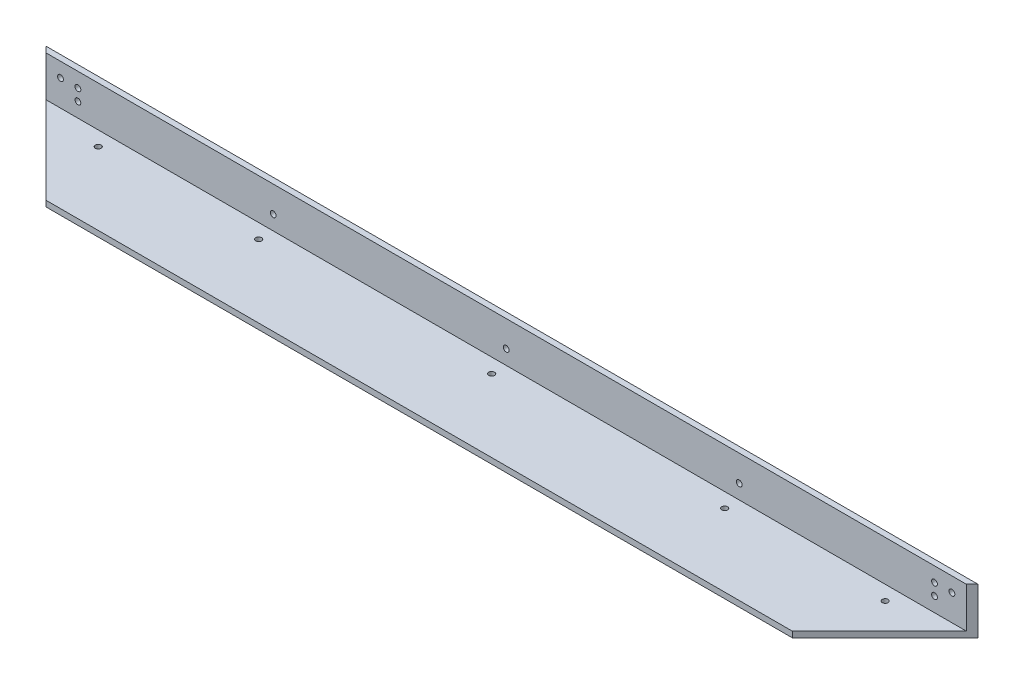
SolidWorks part; units mm, degrees
ref_plane "Front Plane" through (0, 0, 0) normal (0, 0, 1) x (1, 0, 0)
ref_plane "Top Plane" through (0, 0, 0) normal (0, 1, 0) x (1, 0, 0)
ref_plane "Right Plane" through (0, 0, 0) normal (1, 0, 0) x (0, 0, -1)
sketch "Sketch1" plane through (0, 0, 0) normal (1, 0, 0) x (0, 0, -1)
  line L0 (0, 0) -> (-50.8, 0)
  line L1 (-50.8, 0) -> (-50.8, 3.175)
  line L2 (-50.8, 3.175) -> (-3.175, 3.175)
  line L3 (-3.175, 3.175) -> (-3.175, 25.4)
  line L4 (-3.175, 25.4) -> (0, 25.4)
  line L5 (0, 25.4) -> (0, 0)
  dimension "LHeight" = 25.4
  dimension "LWidth" = 50.8
  dimension "LMaterialThickness" = 3.175
  dimension "D1" = 47.625
  dimension "D2" = 22.225
  dimension "D3" = 3.175
extrude "Boss-Extrude1" add sketch "Sketch1" along normal blind 510
chamfer "Chamfer6" distance 50.8 angle 45 1 edges at (510, 1.5875, 50.8)
chamfer "Chamfer7" distance 50.8 angle 45 1 edges at (0, 1.5875, 50.8)
sketch "BackSideHoles-Sketch2" plane through (0, 0, 0) normal (0, 0, -1) x (-1, 0, 0)
  line L0 (0, 0) -> (0, 25.4) construction
  line L1 (-510, 0) -> (0, 0) construction
  line L2 (-510, 0) -> (-510, 25.4) construction
  line L3 (-510, 25.4) -> (0, 25.4) construction
  circle A0 centre (-498.8875, 17.4625) radius 1.5875
  circle A1 centre (-489.3625, 17.4625) radius 1.5875
  circle A2 centre (-20.6375, 17.4625) radius 1.5875
  circle A4 centre (-11.1125, 17.4625) radius 1.5875
  circle A5 centre (-20.6375, 11.1125) radius 1.5875
  circle A6 centre (-489.3625, 11.1125) radius 1.5875
  circle A8 centre (-382.5, 11.1125) radius 1.5875
  circle A9 centre (-255, 11.1125) radius 1.5875
  circle A10 centre (-127.5, 11.1125) radius 1.5875
  dimension "D5" = 3.175
  dimension "D2" = 20.6375
  dimension "D4" = 20.6375
  dimension "D8" = 127.5
  dimension "D9" = 127.5
  dimension "D10" = 127.5
  dimension "D11" = 11.1125
  dimension "D6" = 7.9375
  dimension "D7" = 11.1125
  dimension "D3" = 11.1125
sketch "BottomHoles-Sketch3" plane through (0, 0, 0) normal (0, -1, 0) x (1, 0, 0)
  line L0 (510, 0) -> (0, 0) construction
  circle A7 centre (39.6875, 11.1125) radius 1.5875
  circle A8 centre (470.3125, 11.1125) radius 1.5875
  circle A9 centre (127.5, 11.1125) radius 1.5875
  circle A10 centre (255, 11.1125) radius 1.5875
  circle A11 centre (382.5, 11.1125) radius 1.5875
  dimension "D5" = 3.175
  dimension "D2" = 39.6875
  dimension "D3" = 39.6875
  dimension "D4" = 11.1125
  dimension "D1" = 127.5
  dimension "D6" = 127.5
  dimension "D7" = 127.5
extrude "BottomHoles-Cut-Extrude1" cut sketch "BottomHoles-Sketch3" against normal through all
extrude "BackSideHoles-Cut-Extrude2" cut sketch "BackSideHoles-Sketch2" against normal through all
equation "\"LowerRailWidth\"= 2.00in"
equation "\"LowerRailHeight\"= 1.00in"
equation "\"RailThickness\"= .125in'Spec"
equation "\"SideRailHoleX1FromSide\"= \"HoleOffsetFromSide\""
equation "\"SideRailHoleX2FromSide\"= \"VSWidth\" - \"HoleOffsetFromEdge\" - \"RailThickness\"'Equals 20.6375"
equation "\"SideRailHoleY1FromEdge\"= \"HoleOffsetFromEdge\""
equation "\"FrontBackRailLength\"= 510mm"
equation "\"VSWidth\"= 1.25in'Spec"
equation "\"HoleOffsetFromEdge\"= \"RailThickness\" * 2.5"
equation "\"HoleOffsetFromSide\"= \"RailThickness\" * 3.5"
equation "\"SideRailHoleY2FromSide\"= \"HoleOffsetFromSide\""
equation "\"FasteningHoleDiameter\"= .125in"
equation "\"D1@Boss-Extrude1\"=\"FrontBackRailLength\""
equation "\"D1@Chamfer6\"=\"LowerRailWidth\""
equation "\"D1@Chamfer7\"=\"LowerRailWidth\""
equation "\"D2@BackSideHoles-Sketch2\" = \"SideRailHoleX2FromSide\""
equation "\"D4@BackSideHoles-Sketch2\" = \"SideRailHoleX2FromSide\""
equation "\"D5@BackSideHoles-Sketch2\" = \"FasteningHoleDiameter\""
equation "\"LHeight@Sketch1\"=\"LowerRailHeight\""
equation "\"LWidth@Sketch1\"=\"LowerRailWidth\""
equation "\"LowerCornerBlockWidth\"= \"LowerRailWidth\" - \"RailThickness\" * 2'Room for left front stepper"
equation "\"D2@BottomHoles-Sketch3\"=\"CornerEnclosureOffset\""
equation "\"D3@BottomHoles-Sketch3\"=\"CornerEnclosureOffset\""
equation "\"D4@BottomHoles-Sketch3\"=\"LowerCornerBlockY1FromSide\""
equation "\"D5@BottomHoles-Sketch3\"=\"FasteningHoleDiameter\""
equation "\"CornerEnclosureOffset\"= \"LowerCornerBlockWidth\" - \"HoleOffsetFromEdge\" + \"RailThickness\""
equation "\"LowerCornerBlockY1FromSide\"= \"HoleOffsetFromSide\""
equation "\"FrontOrBackEnclosureOffsets\"= \"FrontBackRailLength\" / 4"
equation "\"D1@BottomHoles-Sketch3\"=\"FrontOrBackEnclosureOffsets\""
equation "\"D6@BottomHoles-Sketch3\"=\"FrontOrBackEnclosureOffsets\""
equation "\"D7@BottomHoles-Sketch3\"=\"FrontOrBackEnclosureOffsets\""
equation "\"D8@BackSideHoles-Sketch2\"=\"FrontOrBackEnclosureOffsets\""
equation "\"D9@BackSideHoles-Sketch2\"=\"FrontOrBackEnclosureOffsets\""
equation "\"D10@BackSideHoles-Sketch2\"=\"FrontOrBackEnclosureOffsets\""
equation "\"D11@BackSideHoles-Sketch2\"=\"SideRailHoleX1FromSide\""
equation "\"D6@BackSideHoles-Sketch2\"=\"SideRailHoleY1FromEdge\""
equation "\"D7@BackSideHoles-Sketch2\"=\"SideRailHoleY2FromSide\""
equation "\"D3@BackSideHoles-Sketch2\"=\"SideRailHoleX1FromSide\""
